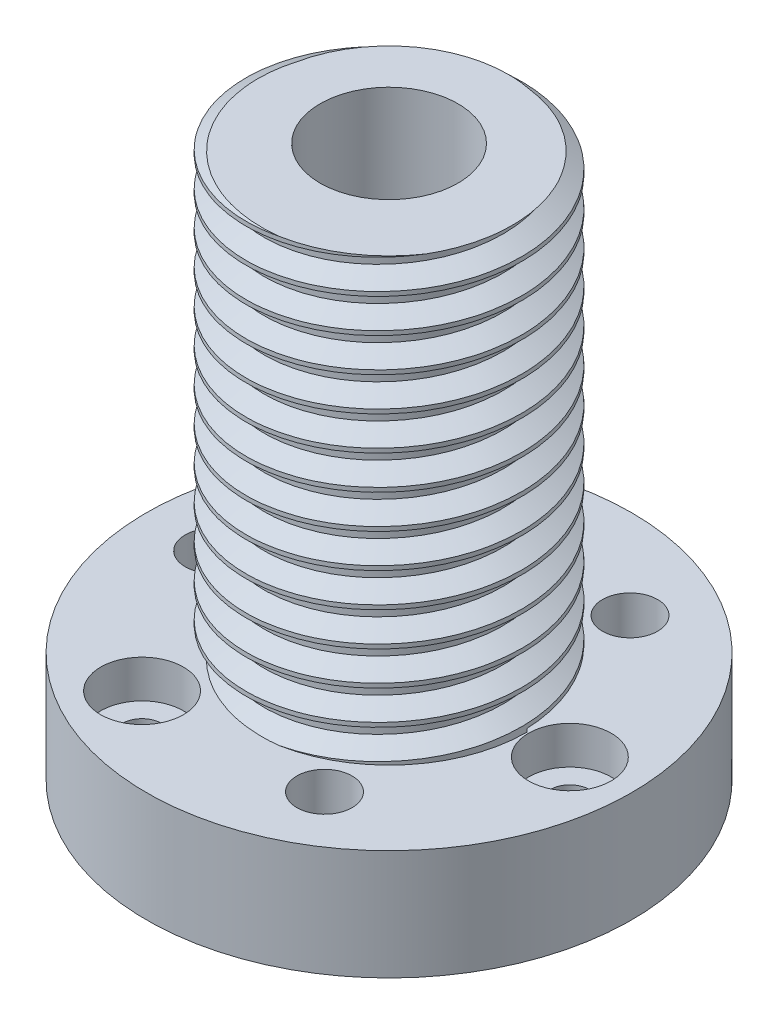
SolidWorks part; units mm, degrees
ref_plane "Front Plane" through (0, 0, 0) normal (0, 0, 1) x (1, 0, 0)
ref_plane "Top Plane" through (0, 0, 0) normal (0, 1, 0) x (1, 0, 0)
ref_plane "Right Plane" through (0, 0, 0) normal (1, 0, 0) x (0, 0, -1)
sketch "Sketch1" plane through (0, 0, 0) normal (0, 1, 0) x (1, 0, 0)
  circle A0 centre (0, 0) radius 7.9375
  dimension "D1" = 15.875
extrude "Boss-Extrude1" add sketch "Sketch1" along normal blind 25.4
sketch "Sketch2" plane through (0, 0, 0) normal (0, -1, 0) x (-1, 0, 0)
  circle A0 centre (0, 0) radius 13.97
  dimension "D1" = 27.94
extrude "Boss-Extrude2" add sketch "Sketch2" along normal blind 6.35
sketch "Sketch3" plane through (0, 25.4, 0) normal (0, 1, 0) x (1, 0, 0)
  circle A0 centre (0, 0) radius 3.9688
  dimension "D1" = 7.9375
extrude "Cut-Extrude1" cut sketch "Sketch3" against normal blind 19.05
hole_wizard "CBORE for #2 Socket Head Cap Screw1" positions "Sketch4" profile "Sketch5" counterbore size "#2" standard "ANSI Inch" end condition through all
sketch "Sketch4" plane through (0, 0, 0) normal (0, 1, 0) x (1, 0, 0)
  line L0 (0, 0) -> (10.414, 0)
  point P0 (10.414, 0)
  point P8 (0, 0)
sketch "Sketch5" plane through (10.414, 0, 0) normal (1, 0, 0) x (0, 0, 1)
  line L0 (0, 0) -> (0, 6.35)
  line L1 (0, 6.35) -> (1.1303, 6.35)
  line L3 (1.1303, 6.35) -> (1.1303, 2.1844)
  line L4 (1.1303, 2.1844) -> (2.3812, 2.1844)
  line L5 (2.3812, 2.1844) -> (2.3812, 0)
  line L7 (2.3812, 0) -> (0, 0)
  line L11 (0, -6.35) -> (0, 107.95) construction
  dimension "Thru Hole Dia." = 2.2606
  dimension "Thru Hole Depth" = 6.35
  dimension "C'Bore Dia." = 4.7625
  dimension "C'Bore Depth" = 2.1844
pattern_circular "CirPattern1" count 3 every 120 about axis through (0, 0, 0) along (0, 1, 0) of "CBORE for #2 Socket Head Cap Screw1"
thread "Thread1" pitch 1.9538 start angle 0, offset 1.524, length 0, pitch 1.9538, diameter 15.875
ref_plane "Plane1" through (7.9375, -1.524, 0) normal (0, 0, 1) x (1, 0, 0)
sketch "Thread Profile1" plane through (7.9375, -1.524, 0) normal (0, 0, 1) x (1, 0, 0)
  line L0 (0, 0) -> (0, 1.9538) construction
  line L11 (0, 0) -> (0, 1.7096)
  line L12 (0, 1.7096) -> (-1.0576, 1.099)
  line L13 (-1.0576, 1.099) -> (-1.0576, 0.6106)
  line L15 (-1.0576, 0.6106) -> (0, 0)
  line L17 (-1.0576, 0.8548) -> (0, 0.8548) construction
  point P2 (0, 0)
  dimension "Pitch" = 1.9538
  dimension "Profile_Angle" = 60
  dimension "Profile_Land" = 0.4885
  dimension "Profile_Height" = 1.0576
sketch "Sketch19" plane through (0, -6.35, 0) normal (0, -1, 0) x (1, 0, 0)
  line L0 (0, 0) -> (0, 1.905)
  line L1 (0, 0) -> (0, -1.905)
  circle A0 centre (0, 0) radius 0.7937
  circle A2 centre (0, 1.905) radius 0.5956
  circle A3 centre (0, -1.905) radius 0.5956
extrude "Cut-Extrude3" cut sketch "Sketch19" against normal blind 11.43 contours A0
hole_wizard "Tap Drill for #0-80 Tap2" positions "Sketch22" profile "Sketch23" hole size "#0-80" standard "ANSI Inch"
sketch "Sketch22" plane through (0, -6.35, 0) normal (0, -1, 0) x (-1, 0, 0)
  point P0 (0, -1.905)
  point P3 (0, 1.905)
sketch "Sketch23" plane through (0, -6.35, 1.905) normal (1, 0, 0) x (0, 0, -1)
  line L0 (0, 0) -> (0, 6.8498)
  line L1 (0, 6.8498) -> (0.5956, 6.35)
  line L2 (0.5956, 6.35) -> (0.5956, 0)
  line L5 (0.5956, 0) -> (0, 0)
  line L10 (0, 6.8498) -> (-0.5956, 6.35) construction
  line L11 (0, -6.35) -> (0, 107.95) construction
  dimension "Hole Dia." = 1.1913
  dimension "Hole Depth" = 6.35
  dimension "Drill Angle" = 100
sketch "Sketch24" plane through (0, 0, 0) normal (0, 1, 0) x (1, 0, 0)
  line L0 (-5.207, 9.0188) -> (0, 0)
  line L1 (0, 0) -> (-5.207, -9.0188)
  line L2 (0, 0) -> (-10.16, 0)
  circle A1 centre (-10.16, 0) radius 1.5875
  point P4 (-5.842, 10.1186)
  point P8 (0, 0)
extrude "Cut-Extrude4" cut sketch "Sketch24" against normal through all contours A1
pattern_circular "CirPattern3" count 3 every 120 about axis through (0, 0, 0) along (0, 1, 0) of "Cut-Extrude4"
